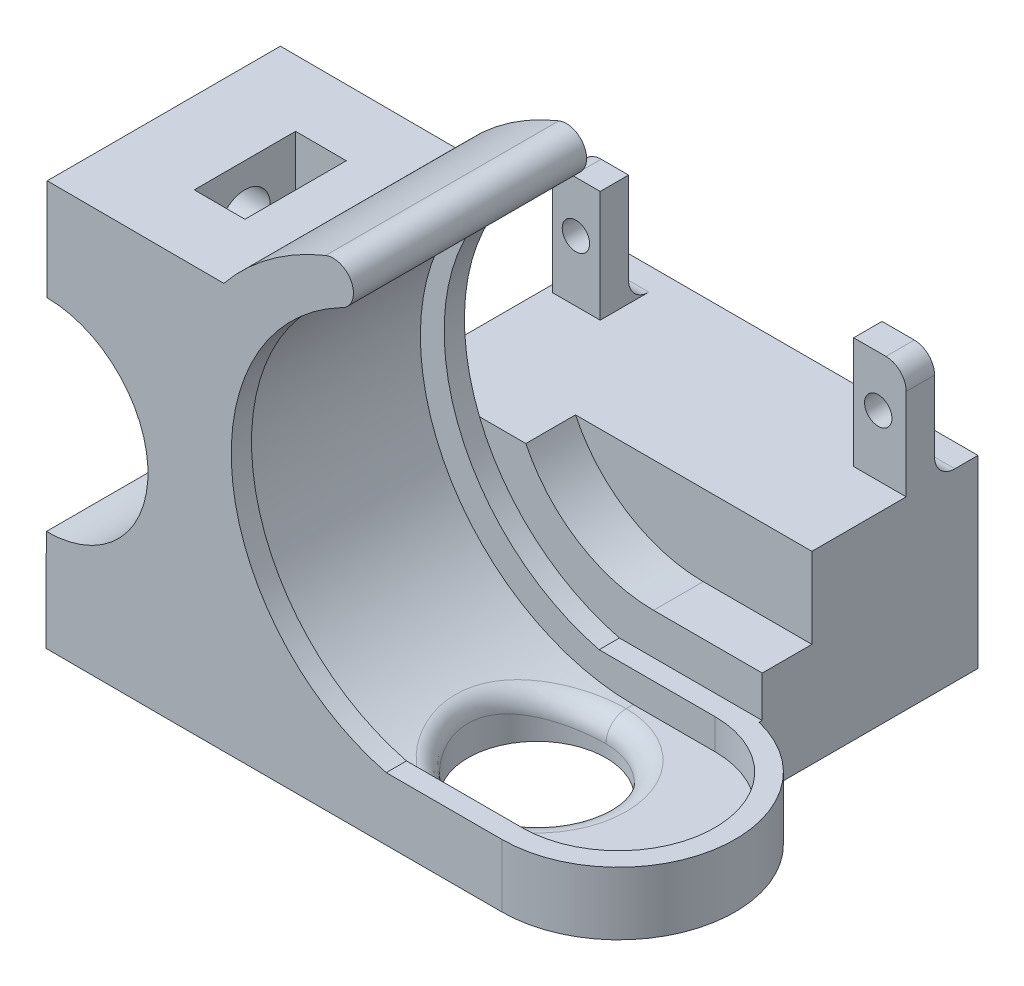
SolidWorks part; units mm, degrees
material "ABS"
ref_plane "Front Plane" through (0, 0, 0) normal (0, 0, 1) x (1, 0, 0)
ref_plane "Top Plane" through (0, 0, 0) normal (0, 1, 0) x (1, 0, 0)
ref_plane "Right Plane" through (0, 0, 0) normal (1, 0, 0) x (0, 0, -1)
sketch "Sketch1" plane through (0, 0, 0) normal (0, 1, 0) x (1, 0, 0)
  line L1 (-31.75, -12.065) -> (31.75, -12.065)
  line L2 (-31.75, -12.065) -> (-31.75, 12.065)
  line L3 (-31.75, 12.065) -> (31.75, 12.065)
  line L4 (31.75, -12.065) -> (31.75, 12.065)
  line L5 (-31.75, -12.065) -> (31.75, 12.065) construction
  line L6 (-31.75, 12.065) -> (31.75, -12.065) construction
  point P0 (0, 0)
  dimension "D1" = 24.13
  dimension "D2" = 63.5
extrude "Boss-Extrude1" add sketch "Sketch1" along normal blind 4.064
sketch "Sketch2" plane through (0, 0, 0) normal (0, 0, 1) x (1, 0, 0)
  line L0 (0, -2.2352) -> (0, 2.2352) construction
  line L1 (-31.75, 4.064) -> (31.75, 4.064) construction
  line L3 (-31.75, 4.064) -> (31.75, 4.064) construction
  line L4 (0, 4.064) -> (-26.7168, 4.064)
  line L5 (-31.571, 27.3677) -> (-26.7168, 4.064)
  arc A0 (-9.9723, 55.4695) -> (0, 4.064) centre (0, 30.734) ccw
  arc A1 (-11.8717, 60.181) -> (-31.571, 27.3677) centre (0, 30.734) ccw
  arc A2 (-9.9723, 55.4695) -> (-11.8717, 60.181) centre (-10.922, 57.8252) ccw
  dimension "D1" = 53.34
  dimension "D2" = 63.5
  dimension "D3" = 10.922
  dimension "D4" = 23.3037
  dimension "D5" = 23.8039
extrude "Boss-Extrude2" add sketch "Sketch2" along normal up to surface and the other way up to surface up to face at (0, 2.032, 12.065) other way up to face at (0, 2.032, -12.065)
sketch "Sketch4" plane through (0, 4.064, 0) normal (0, 1, 0) x (1, 0, 0)
  circle A0 centre (0, 0) radius 8.636
  dimension "D1" = 17.272
extrude "Cut-Extrude1" cut sketch "Sketch4" against normal through all and the other way blind 4.064
fillet "Fillet1" radius 2.54 2 edges at (8.636, 4.064, 0) (-8.5992, 5.4884, 0.7963)
sketch "Sketch6" plane through (0, 0, 12.065) normal (0, 0, 1) x (1, 0, 0)
  line L0 (-31.75, 4.064) -> (-26.7168, 4.064)
  line L1 (-26.7168, 4.064) -> (-25.8702, 0)
  line L2 (-25.8702, 0) -> (-31.75, 0)
  line L3 (-31.75, 4.064) -> (-31.75, 0) construction
  line L4 (-31.75, 0) -> (-31.75, 4.064)
  dimension "D1" = 4.1512
extrude "Cut-Extrude2" cut sketch "Sketch6" against normal through all
sketch "Sketch8" plane through (0, 0, 12.065) normal (0, 0, 1) x (1, 0, 0)
  line L0 (31.75, 0) -> (31.75, 7.874)
  line L1 (0, 4.064) -> (31.75, 4.064) construction
  line L2 (31.75, 0) -> (-25.8702, 0)
  line L3 (-25.8702, 0) -> (-31.571, 27.3677)
  line L4 (31.75, 7.874) -> (-23.9497, 7.874) construction
  line L5 (-4.2746, 7.874) -> (31.75, 7.874)
  arc A0 (-31.571, 27.3677) -> (-11.8717, 60.181) centre (0, 30.734) cw
  arc A1 (-11.8717, 60.181) -> (-9.9723, 55.4695) centre (-10.922, 57.8252) cw
  arc A2 (-9.9723, 55.4695) -> (-4.2746, 7.874) centre (1.9655, 32.7598) ccw
  dimension "D1" = 3.81
extrude "Boss-Extrude3" add sketch "Sketch8" along normal blind 2.54
sketch "Sketch9" plane through (0, 0, -12.065) normal (0, 0, -1) x (-1, 0, 0)
  line L0 (-31.75, 0) -> (-31.75, 7.874)
  line L1 (-31.75, 7.874) -> (4.2746, 7.874)
  line L2 (-31.75, 0) -> (25.8702, 0)
  line L3 (25.8702, 0) -> (31.571, 27.3677)
  arc A0 (31.571, 27.3677) -> (11.8717, 60.181) centre (0, 30.734) ccw
  arc A2 (9.9723, 55.4695) -> (4.2746, 7.874) centre (-1.9655, 32.7598) cw
  arc A3 (11.8717, 60.181) -> (9.9723, 55.4695) centre (10.922, 57.8252) ccw
extrude "Boss-Extrude4" add sketch "Sketch9" along normal blind 2.54
sketch "Sketch10" plane through (0, 4.064, 0) normal (0, 1, 0) x (1, 0, 0)
  line L0 (10.2183, 14.605) -> (10.2183, -14.605) construction
  line L3 (-4.2746, 14.605) -> (31.75, 14.605) construction
  line L4 (31.75, -14.605) -> (-4.2746, -14.605) construction
  line L5 (10.2183, 14.605) -> (10.2183, 12.065)
  line L6 (10.2183, -12.065) -> (10.2183, -14.605)
  arc A2 (10.2183, 14.605) -> (10.2183, -14.605) centre (10.2183, 0) cw
  arc A3 (10.2183, -12.065) -> (10.2183, 12.065) centre (10.2183, 0) ccw
extrude "Boss-Extrude5" add sketch "Sketch10" along normal blind 3.81
sketch "Sketch11" plane through (0, 7.874, 0) normal (0, 1, 0) x (1, 0, 0)
  line L0 (10.2183, 12.065) -> (10.2183, -12.065) construction
  line L1 (10.2183, 14.605) -> (10.2183, -14.605) construction
  line L2 (-4.2746, 14.605) -> (31.75, 14.605) construction
  line L3 (31.75, -14.605) -> (-4.2746, -14.605) construction
  line L4 (10.2183, 14.605) -> (31.75, 14.605)
  line L5 (31.75, 14.605) -> (31.75, -14.605)
  line L6 (31.75, -14.605) -> (10.2183, -14.605)
  arc A0 (10.2183, -14.605) -> (10.2183, 14.605) centre (10.2183, 0) ccw
extrude "Cut-Extrude3" cut sketch "Sketch11" against normal through all
sketch "Sketch12" plane through (0, 0, 0) normal (0, -1, 0) x (1, 0, 0)
  line L0 (-25.8702, -14.605) -> (-31.571, -14.605) construction
  line L1 (-31.2166, -14.605) -> (13.6144, -14.605)
  line L2 (-31.2166, -14.605) -> (-31.2166, -41.632)
  line L3 (-31.2166, -41.632) -> (13.6144, -41.632)
  line L4 (13.6144, -14.605) -> (13.6144, -41.632)
extrude "Boss-Extrude6" add sketch "Sketch12" against normal up to surface (23.114 mm away) up to face at (-6.2783, 14.6544, 12.065)
sketch "Sketch13" plane through (0, 0, 0) normal (0, -1, 0) x (1, 0, 0)
  line L0 (10.2183, -14.605) -> (13.6144, -14.605)
  line L1 (13.6144, -14.605) -> (13.6144, -13.3355)
  line L2 (13.6144, -13.3355) -> (10.2183, -14.605)
extrude "Boss-Extrude7" add sketch "Sketch13" against normal up to surface (7.874 mm away) up to face at (6.3056, 7.874, 0)
sketch "Sketch14" plane through (0, 0, -14.605) normal (0, 0, 1) x (1, 0, 0)
  line L0 (0, 13.0173) -> (18.6203, 13.0173)
  line L1 (18.6203, 13.0173) -> (17.7167, 30.734)
  arc A0 (17.7167, 30.734) -> (0, 13.0173) centre (0, 30.734) ccw
extrude "Cut-Extrude4" cut sketch "Sketch14" against normal up to surface (6.2198 mm away) up to face at (7.2796, 4.064, 0)
sketch "Sketch16" plane through (0, 0, -14.605) normal (0, 0, 1) x (1, 0, 0)
  line L0 (-31.2166, 23.114) -> (-30.685, 23.114)
  line L1 (-30.685, 23.114) -> (-25.8702, 0)
  line L2 (-25.8702, 0) -> (-31.2166, 0)
  line L3 (-31.2166, 0) -> (-31.2166, 23.114)
extrude "Cut-Extrude5" cut sketch "Sketch16" against normal up to surface (27.027 mm away) up to face at (-8.8011, 11.557, -41.632)
sketch "Sketch17" plane through (0, 23.114, 0) normal (0, 1, 0) x (1, 0, 0)
  line L0 (13.6144, 41.632) -> (13.6144, 20.8248) construction
  line L1 (6.6167, 32.6358) -> (13.6144, 32.6358)
  line L2 (6.6167, 32.6358) -> (6.6167, 36.1918)
  line L3 (6.6167, 36.1918) -> (13.6144, 36.1918)
  line L4 (13.6144, 32.6358) -> (13.6144, 36.1918)
  dimension "D1" = 3.556
extrude "Boss-Extrude8" add sketch "Sketch17" along normal blind 13.97
sketch "Sketch18" plane through (0, 23.114, 0) normal (0, 1, 0) x (1, 0, 0)
  line L0 (-30.685, 41.632) -> (-30.685, 14.605) construction
  line L1 (-24.2951, 32.6358) -> (-30.685, 32.6358)
  line L2 (-24.2951, 32.6358) -> (-24.2951, 36.1918)
  line L3 (-24.2951, 36.1918) -> (-30.685, 36.1918)
  line L4 (-30.685, 32.6358) -> (-30.685, 36.1918)
  dimension "D1" = 3.556
extrude "Boss-Extrude9" add sketch "Sketch18" along normal blind 13.97
sketch "Sketch19" plane through (0, 37.084, 0) normal (0, 1, 0) x (1, 0, 0)
  line L0 (-24.2951, 36.1918) -> (6.6167, 36.1918) construction
  line L1 (6.6167, 32.6358) -> (13.6144, 32.6358) construction
  line L2 (-24.7142, 39.7478) -> (7.0358, 39.7478)
  line L3 (-24.7142, 39.7478) -> (-24.7142, 32.6358)
  line L4 (-24.7142, 32.6358) -> (7.0358, 32.6358)
  line L5 (7.0358, 39.7478) -> (7.0358, 32.6358)
  line L6 (-24.7142, 39.7478) -> (7.0358, 32.6358) construction
  line L7 (-24.7142, 32.6358) -> (7.0358, 39.7478) construction
  point P4 (-8.8392, 36.1918)
  dimension "D1" = 31.75
extrude "Cut-Extrude6" cut sketch "Sketch19" against normal up to surface (13.97 mm away) up to face at (-10.4957, 23.114, -29.6026)
sketch "Sketch20" plane through (0, 0, -36.1918) normal (0, 0, -1) x (-1, 0, 0)
  circle A0 centre (27.7559, 30.734) radius 1.7145
  circle A1 centre (-10.1155, 30.734) radius 1.7145
  dimension "D1" = 3.429
  dimension "D2" = 3.429
extrude "Cut-Extrude7" cut sketch "Sketch20" against normal up to surface (3.556 mm away)
fillet "Fillet2" radius 2.54 1 edges at (10.3251, 23.114, -36.1918)
fillet "Fillet3" radius 2.54 1 edges at (-27.6996, 23.114, -36.1918)
fillet "Fillet4" radius 2.54 2 edges at (13.6144, 37.084, -34.4138) (-30.685, 37.084, -34.4138)
ref_plane "Plane1" through (-31.571, 0, 0) normal (1, 0, 0) x (0, 0, -1)
ref_plane "Plane2" through (0, 0, 0) normal (0, -1, 0) x (-1, 0, 0)
ref_plane "Plane3" through (0, 0, 14.605) normal (0, 0, 1) x (1, 0, 0)
sketch "Sketch26" plane through (0, 0, 14.605) normal (0, 0, 1) x (1, 0, 0)
  line L0 (-25.8702, 0) -> (-31.6536, 0)
  line L1 (-31.6536, 0) -> (-31.571, 27.3677)
  line L2 (-31.571, 27.3677) -> (-25.8702, 0)
extrude "Boss-Extrude10" add sketch "Sketch26" against normal blind 29.21
ref_plane "Plane4" through (0, 0, -41.632) normal (0, 0, -1) x (-1, 0, 0)
sketch "Sketch27" plane through (0, 0, -41.632) normal (0, 0, -1) x (-1, 0, 0)
  line L0 (30.685, 23.114) -> (30.685, 0)
  line L1 (30.685, 0) -> (25.8702, 0)
  line L2 (25.8702, 0) -> (30.685, 23.114) construction
  line L3 (25.8702, 0) -> (-13.6144, 0) construction
  line L4 (25.8702, 0) -> (30.685, 23.114)
extrude "Boss-Extrude11" add sketch "Sketch27" against normal blind 27.178
sketch "Sketch28" plane through (-30.685, 0, 0) normal (-1, 0, 0) x (0, 0, 1)
  line L0 (-41.632, 0) -> (-14.605, 0)
  line L1 (-30.9304, 0) -> (30.9304, 0) construction
  line L2 (-41.632, 12.7127) -> (-41.632, -12.7127) construction
  line L3 (-14.605, 0) -> (-14.605, 23.114)
  line L4 (-14.605, 23.114) -> (-41.632, 23.114)
  line L5 (-41.632, 23.114) -> (-41.632, 0)
extrude "Boss-Extrude12" add sketch "Sketch28" along normal blind 0.889
sketch "Sketch29" plane through (-31.6533, 0.0954, 0) normal (-1, 0.003, 0) x (0, 0, 1)
  line L0 (14.605, 27.2724) -> (14.605, 60.1449) construction
  line L1 (-14.605, -0.0954) -> (14.605, -0.0954)
  line L2 (-14.605, -0.0954) -> (-14.605, 50.7046)
  line L3 (-14.605, 50.7046) -> (14.605, 50.7046)
  line L4 (14.605, -0.0954) -> (14.605, 50.7046)
  dimension "D1" = 50.8
  dimension "D2" = 29.21
extrude "Boss-Extrude13" add sketch "Sketch29" along normal blind 15.24
sketch "Sketch30" plane through (0, 0, 14.605) normal (0, 0, 1) x (1, 0, 0)
  line L0 (-46.8935, 0.046) -> (-46.7403, 50.8457) construction
  circle A0 centre (-46.8169, 25.4458) radius 12.7
  dimension "D1" = 25.4
extrude "Cut-Extrude8" cut sketch "Sketch30" against normal blind 30.48
sketch "Sketch31" plane through (-31.6533, 0.0954, 0) normal (1, -0.003, 0) x (0, 0, -1)
  line L1 (-14.605, 34.1953) -> (14.605, 34.1953)
  line L2 (-14.605, 34.1953) -> (-14.605, 50.7046)
  line L3 (-14.605, 50.7046) -> (14.605, 50.7046)
  line L4 (14.605, 34.1953) -> (14.605, 50.7046)
extrude "Boss-Extrude14" add sketch "Sketch31" along normal up to surface up to face at (-23.4941, 48.5911, 0)
sketch "Sketch32" plane through (-46.8932, 0.1414, 0) normal (-1, 0.003, 0) x (0, 0, 1)
  line L0 (-14.605, 50.7046) -> (14.605, 50.7046) construction
  circle A0 centre (0, 44.3546) radius 3.175
  dimension "D1" = 6.35
  dimension "D2" = 6.35
extrude "Cut-Extrude9" cut sketch "Sketch32" against normal blind 12.7
sketch "Sketch33" plane through (-46.8932, 0.1414, 0) normal (-1, 0.003, 0) x (0, 0, 1)
  line L0 (-14.605, -0.0954) -> (14.605, -0.0954) construction
  circle A0 centre (0, 6.2546) radius 3.175
  dimension "D1" = 6.35
  dimension "D2" = 6.35
extrude "Cut-Extrude10" cut sketch "Sketch33" against normal blind 12.7
sketch "Sketch34" plane through (0.1529, 50.7043, 0) normal (0.003, 1, 0) x (1, -0.003, 0)
  line L0 (-46.8934, 0) -> (-24.7753, 0) construction
  line L1 (-36.7334, -6.35) -> (-30.3834, -6.35)
  line L2 (-36.7334, -6.35) -> (-36.7334, 6.35)
  line L3 (-36.7334, 6.35) -> (-30.3834, 6.35)
  line L4 (-30.3834, -6.35) -> (-30.3834, 6.35)
  line L5 (-46.8934, -14.605) -> (-46.8934, 14.605) construction
  line L6 (-24.7753, 14.605) -> (-24.7753, -14.605) construction
  dimension "D1" = 12.7
  dimension "D2" = 6.35
  dimension "D3" = 6.35
  dimension "D4" = 10.16
extrude "Cut-Extrude11" cut sketch "Sketch34" against normal blind 11.43
sketch "Sketch35" plane through (-0.0003, -0.0954, 0) normal (-0.003, -1, 0) x (1, -0.003, 0)
  line L0 (-46.8934, 0) -> (-31.6534, 0) construction
  line L1 (-40.5434, 6.35) -> (-34.1934, 6.35)
  line L2 (-40.5434, 6.35) -> (-40.5434, -6.35)
  line L3 (-40.5434, -6.35) -> (-34.1934, -6.35)
  line L4 (-34.1934, 6.35) -> (-34.1934, -6.35)
  line L5 (-46.8934, -14.605) -> (-46.8934, 14.605) construction
  line L6 (-31.6534, -14.605) -> (-31.6534, 14.605) construction
  dimension "D1" = 6.35
  dimension "D2" = 12.7
  dimension "D3" = 6.35
  dimension "D4" = 6.35
extrude "Cut-Extrude12" cut sketch "Sketch35" against normal blind 11.43
